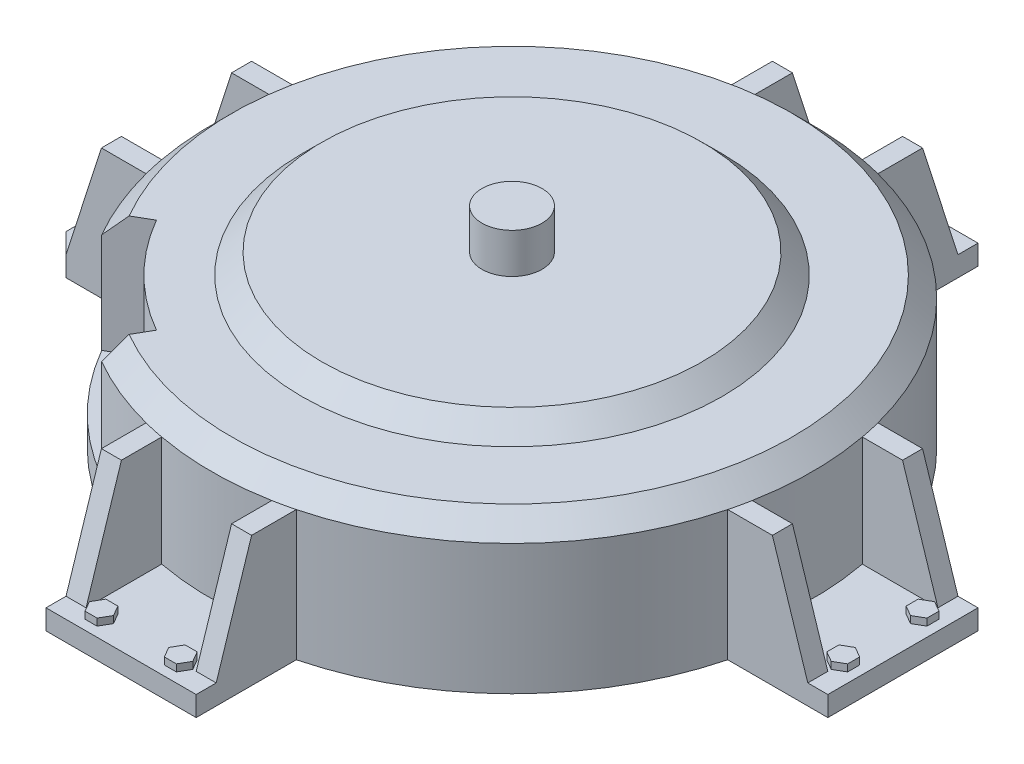
SolidWorks part; units mm, degrees
ref_plane "Front Plane" through (0, 0, 0) normal (0, 0, 1) x (1, 0, 0)
ref_plane "Top Plane" through (0, 0, 0) normal (0, 1, 0) x (1, 0, 0)
ref_plane "Right Plane" through (0, 0, 0) normal (1, 0, 0) x (0, 0, -1)
sketch "Sketch2" plane through (0, 0, 0) normal (0, 1, 0) x (1, 0, 0)
  circle A0 centre (0, 0) radius 150
  dimension "D1" = 300
extrude "Boss-Extrude1" add sketch "Sketch2" along normal blind 75
chamfer "Chamfer1" distance 10 angle 45 1 edges at (0, 75, 150)
sketch "Sketch3" plane through (0, 0, 0) normal (0, -1, 0) x (1, 0, 0)
  line L1 (-195.2369, 37.5) -> (-145.2369, 37.5)
  line L2 (-195.2369, 37.5) -> (-195.2369, -37.5)
  line L3 (-195.2369, -37.5) -> (-145.2369, -37.5)
  circle A0 centre (0, 0) radius 150 construction
  circle A1 centre (0, 0) radius 150
  point P0 (-150, 0)
  circle M6 centre (0, 0) radius 150
  dimension "D2" = 50
  dimension "D1" = 75
extrude "Boss-Extrude2" add sketch "Sketch3" against normal blind 10 contours L2 L3 L1 M6 region at (-171.8083, 0, 0)
chamfer "Chamfer2" distance 10 angle 45 2 edges at (-195.2369, 5, 37.5) (-195.2369, 5, -37.5)
sketch "Sketch6" plane through (0, 0, 37.5) normal (0, 0, 1) x (1, 0, 0)
  line L0 (-145.2369, 10) -> (-145.2369, 65)
  line L1 (-150, 65) -> (150, 65) construction
  line L2 (-145.2369, 65) -> (-167.5569, 65)
  line L3 (-167.5569, 65) -> (-185.2369, 10)
  line L4 (-185.2369, 10) -> (-145.2369, 10)
  line L5 (-185.2369, 10) -> (-185.2369, 0) construction
  line L6 (-185.2369, 10) -> (-145.2369, 10) construction
  dimension "D1" = 17.68
extrude "Boss-Extrude4" add sketch "Sketch6" against normal blind 10
sketch "Sketch7" plane through (0, 10, 0) normal (0, 1, 0) x (1, 0, 0)
  line L0 (-185.2369, 37.5) -> (-185.2369, -53.0021) construction
  line L2 (-185.2369, -25.8032) -> (-180.0407, -22.8032)
  line L3 (-180.0407, -22.8032) -> (-180.0407, -16.8032)
  line L4 (-180.0407, -16.8032) -> (-185.2369, -13.8032)
  line L5 (-185.2369, -13.8032) -> (-190.433, -16.8032)
  line L6 (-190.433, -16.8032) -> (-190.433, -22.8032)
  line L7 (-190.433, -22.8032) -> (-185.2369, -25.8032)
  circle A0 centre (-185.2369, -19.8032) radius 5.1962 construction
  dimension "D1" = 6
extrude "Boss-Extrude5" add sketch "Sketch7" along normal blind 3.5
mirror "Mirror1" about plane through (0, 0, 0) normal (0, 0, 1) of "Boss-Extrude5", "Boss-Extrude4"
pattern_circular "CirPattern11" count 4 over 360 about axis through (0, 0, 0) along (0, 1, 0) of "Boss-Extrude2", "Boss-Extrude4", "Mirror1"
sketch "Sketch8" plane through (0, 75, 0) normal (0, 1, 0) x (1, 0, 0)
  line L2 (-65, -112.5833) -> (-75, -129.9038)
  line L3 (-112.5833, -65) -> (-129.9038, -75)
  arc A0 (-112.5833, -65) -> (-65, -112.5833) centre (0, 0) ccw
  arc A1 (-145.2369, -37.5) -> (-37.5, -145.2369) centre (0, 0) ccw construction
  arc A2 (-129.9038, -75) -> (-75, -129.9038) centre (0, 0) ccw
extrude "Cut-Extrude1" cut sketch "Sketch8" against normal blind 60
sketch "Sketch9" plane through (0, 75, 0) normal (0, 1, 0) x (1, 0, 0)
  circle A0 centre (0, 0) radius 110
  dimension "D1" = 220
extrude "Boss-Extrude6" add sketch "Sketch9" along normal blind 10
chamfer "Chamfer3" distance 15 angle 45 1 edges at (0, 85, 110)
sketch "Sketch10" plane through (0, 85, 0) normal (0, 1, 0) x (1, 0, 0)
  circle A0 centre (0, 0) radius 15
  dimension "D1" = 30
extrude "Boss-Extrude7" add sketch "Sketch10" along normal blind 20
